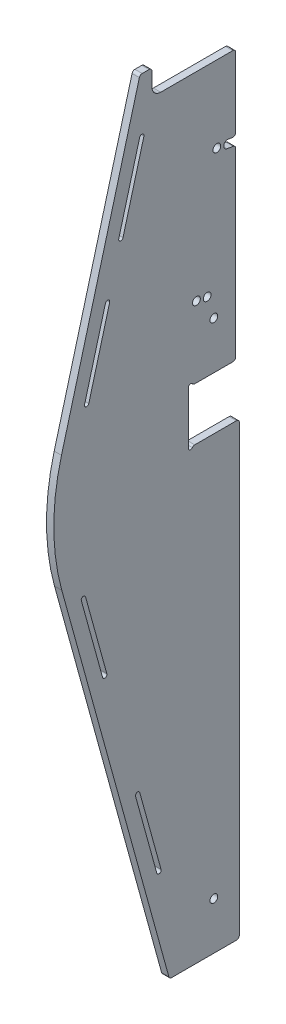
SolidWorks part; units mm, degrees
material "PC High Viscosity"
ref_plane "Front Plane" through (0, 0, 0) normal (0, 0, 1) x (1, 0, 0)
ref_plane "Top Plane" through (0, 0, 0) normal (0, 1, 0) x (1, 0, 0)
ref_plane "Right Plane" through (0, 0, 0) normal (1, 0, 0) x (0, 0, -1)
sketch "ReferenceGeometry" plane through (0, 0, 0) normal (1, 0, 0) x (0, 0, -1)
  line L0 (0, 0) -> (-63.5, -234.95)
  line L1 (-63.5, -234.95) -> (-63.5, -279.4)
  line L2 (31.75, -234.4263) -> (34.8815, -234.95)
  line L3 (76.2, 0) -> (82.55, 0)
  line L4 (31.75, -234.95) -> (76.2, -234.95)
  line L5 (31.75, -234.95) -> (31.75, -279.4)
  line L6 (31.75, -279.4) -> (76.2, -279.4)
  line L7 (76.2, -234.95) -> (76.2, -279.4)
  line L8 (31.75, -673.1) -> (76.2, -673.1)
  line L9 (31.75, -673.1) -> (31.75, -717.55)
  line L10 (31.75, -717.55) -> (76.2, -717.55)
  line L11 (76.2, -673.1) -> (76.2, -717.55)
  line L12 (31.75, -234.4263) -> (69.8935, -6.35)
  line L13 (34.8815, -234.95) -> (73.025, -6.8737)
  line L14 (69.8935, -6.35) -> (73.025, -6.8737)
  line L15 (-63.5, -279.4) -> (31.75, -673.1)
  line L17 (76.2, 0) -> (73.025, 0)
  line L18 (76.2, 0) -> (76.2, -234.95)
  line L19 (76.2, -234.95) -> (73.025, -234.95)
  line L20 (73.025, 0) -> (73.025, -234.95)
  line L21 (0, 0) -> (6.35, 0) construction
  line L22 (0, 0) -> (0, 50.8) construction
  line L23 (0, 50.8) -> (6.35, 50.8) construction
  line L24 (6.35, 0) -> (6.35, 50.8) construction
  dimension "D1" = 44.45
  dimension "D2" = 438.15
  dimension "D3" = 6.35
  dimension "D4" = 6.35
  dimension "D5" = 234.95
  dimension "D6" = 3.175
  dimension "D7" = 3.175
  dimension "D8" = 6.35
  dimension "D9" = 95.25
  dimension "D10" = 231.2439
  dimension "D11" = 50.8
  dimension "D12" = 66.675
sketch "CoreWall" plane through (0, 0, 0) normal (1, 0, 0) x (0, 0, -1)
  line L0 (73.025, -234.95) -> (31.75, -234.95)
  line L1 (0, 0) -> (73.025, 0)
  line L2 (73.025, -234.95) -> (73.025, 0)
  line L3 (31.75, -234.95) -> (31.75, -280.9875)
  line L4 (31.75, -280.9875) -> (76.2, -280.9875)
  line L5 (76.2, -234.95) -> (76.2, -279.4) construction
  line L6 (31.75, -279.4) -> (76.2, -279.4) construction
  line L7 (76.2, -280.9875) -> (76.2, -673.1)
  line L8 (76.2, -673.1) -> (31.75, -673.1)
  line L9 (0, 0) -> (-63.5, -234.95)
  line L10 (-63.2591, -328.6115) -> (31.75, -673.1)
  arc A0 (-63.5, -234.95) -> (-63.2591, -328.6115) centre (108.1416, -281.3396) ccw
  dimension "D2" = 177.8
  dimension "D1" = 1.5875
sketch "WallTabAdder" plane through (0, 0, 0) normal (1, 0, 0) x (0, 0, -1)
  line L0 (0, 0) -> (-63.5, -234.95) construction
  line L1 (-63.2591, -328.6115) -> (31.75, -673.1) construction
  line L2 (0, 0) -> (-63.5, -234.95)
  line L3 (-63.2591, -328.6115) -> (31.75, -673.1)
  line L4 (-16.4446, 0) -> (-78.8251, -230.8081)
  line L5 (-78.5627, -332.8322) -> (15.2823, -673.1)
  line L6 (-78.5627, -332.8322) -> (16.4464, -677.3207) construction
  line L7 (15.2823, -673.1) -> (31.75, -673.1)
  line L8 (-15.3251, 4.1419) -> (-78.8251, -230.8081) construction
  line L9 (-16.4446, 0) -> (0, 0)
  line L10 (-27.0627, -92.8306) -> (-8.8382, -25.4) construction
  line L11 (-28.9017, -92.3336) -> (-10.6772, -24.903)
  line L12 (-25.2237, -93.3277) -> (-6.9992, -25.897)
  line L13 (6.1311, -587.375) -> (-12.44, -520.039) construction
  line L14 (4.2947, -587.8815) -> (-14.2764, -520.5455)
  line L15 (7.9676, -586.8685) -> (-10.6035, -519.5325)
  line L16 (-41.1408, -415.9743) -> (-59.7119, -348.6383) construction
  line L17 (-42.9772, -416.4808) -> (-61.5483, -349.1448)
  line L18 (-39.3044, -415.4678) -> (-57.8755, -348.1318)
  line L19 (-56.8846, -203.1717) -> (-38.6601, -135.741) construction
  line L20 (-58.7236, -202.6746) -> (-40.4991, -135.244)
  line L21 (-55.0456, -203.6687) -> (-36.8211, -136.2381)
  arc A0 (-63.5, -234.95) -> (-63.2591, -328.6115) centre (108.1416, -281.3396) ccw construction
  arc A1 (-63.5, -234.95) -> (-63.2591, -328.6115) centre (108.1416, -281.3396) ccw
  arc A2 (-78.8251, -230.8081) -> (-78.5627, -332.8322) centre (108.1416, -281.3396) ccw
  arc A3 (-28.9017, -92.3336) -> (-25.2237, -93.3277) centre (-27.0627, -92.8306) ccw
  arc A4 (-6.9992, -25.897) -> (-10.6772, -24.903) centre (-8.8382, -25.4) ccw
  arc A5 (4.2947, -587.8815) -> (7.9676, -586.8685) centre (6.1311, -587.375) ccw
  arc A6 (-10.6035, -519.5325) -> (-14.2764, -520.5455) centre (-12.44, -520.039) ccw
  arc A7 (-42.9772, -416.4808) -> (-39.3044, -415.4678) centre (-41.1408, -415.9743) ccw
  arc A8 (-57.8755, -348.1318) -> (-61.5483, -349.1448) centre (-59.7119, -348.6383) ccw
  arc A9 (-58.7236, -202.6746) -> (-55.0456, -203.6687) centre (-56.8846, -203.1717) ccw
  arc A10 (-36.8211, -136.2381) -> (-40.4991, -135.244) centre (-38.6601, -135.741) ccw
  point P14 (-17.9505, -59.1153)
  point P20 (-3.1544, -553.707)
  point P27 (-50.4263, -382.3063)
  point P35 (-47.7724, -169.4564)
  dimension "D2" = 69.85
  dimension "D3" = 3.81
  dimension "D4" = 25.4
  dimension "D5" = 85.725
  dimension "D6" = 107.95
  dimension "D7" = 44.45
  dimension "D1" = 15.875
sketch "Sketch4" plane through (0, 0, 0) normal (1, 0, 0) x (0, 0, -1)
  line L1 (31.75, -280.9875) -> (76.2, -280.9875) construction
  line L2 (76.2, -280.9875) -> (76.2, -673.1) construction
  line L3 (31.75, -673.1) -> (76.2, -673.1) construction
  line L4 (15.2823, -673.1) -> (31.75, -673.1) construction
  line L5 (-78.5627, -332.8322) -> (15.2823, -673.1) construction
  line L6 (-16.4446, 0) -> (-78.8251, -230.8081) construction
  line L7 (-16.4446, 0) -> (0, 0) construction
  line L8 (0, 0) -> (73.025, 0) construction
  line L9 (73.025, 0) -> (73.025, -234.95) construction
  line L10 (31.75, -234.95) -> (31.75, -280.9875) construction
  line L11 (31.75, -280.9875) -> (76.2, -280.9875)
  line L12 (76.2, -280.9875) -> (76.2, -673.1)
  line L13 (31.75, -673.1) -> (76.2, -673.1)
  line L14 (15.2823, -673.1) -> (31.75, -673.1)
  line L15 (-78.5627, -332.8322) -> (15.2823, -673.1)
  line L16 (-16.4446, 0) -> (-78.8251, -230.8081)
  line L17 (-16.4446, 0) -> (0, 0)
  line L18 (0, 0) -> (73.025, 0)
  line L19 (73.025, 0) -> (73.025, -234.95)
  line L20 (73.025, -234.95) -> (31.75, -234.95)
  line L21 (-28.9017, -92.3336) -> (-10.6772, -24.903) construction
  line L22 (-28.9017, -92.3336) -> (-10.6772, -24.903)
  line L23 (-25.2237, -93.3277) -> (-6.9992, -25.897) construction
  line L24 (-25.2237, -93.3277) -> (-6.9992, -25.897)
  line L25 (31.75, -234.95) -> (31.75, -280.9875)
  line L26 (-42.9772, -416.4808) -> (-61.5483, -349.1448) construction
  line L27 (-42.9772, -416.4808) -> (-61.5483, -349.1448)
  line L28 (-39.3044, -415.4678) -> (-57.8755, -348.1318) construction
  line L29 (-39.3044, -415.4678) -> (-57.8755, -348.1318)
  line L30 (7.9676, -586.8685) -> (-10.6035, -519.5325) construction
  line L31 (7.9676, -586.8685) -> (-10.6035, -519.5325)
  line L32 (4.2947, -587.8815) -> (-14.2764, -520.5455) construction
  line L33 (4.2947, -587.8815) -> (-14.2764, -520.5455)
  line L34 (-58.7236, -202.6746) -> (-40.4991, -135.244) construction
  line L35 (-58.7236, -202.6746) -> (-40.4991, -135.244)
  line L36 (-55.0456, -203.6687) -> (-36.8211, -136.2381) construction
  line L37 (-55.0456, -203.6687) -> (-36.8211, -136.2381)
  arc A0 (-78.8251, -230.8081) -> (-78.5627, -332.8322) centre (108.1416, -281.3396) ccw construction
  arc A1 (-6.9992, -25.897) -> (-10.6772, -24.903) centre (-8.8382, -25.4) ccw construction
  arc A2 (-78.8251, -230.8081) -> (-78.5627, -332.8322) centre (108.1416, -281.3396) ccw
  arc A3 (-6.9992, -25.897) -> (-10.6772, -24.903) centre (-8.8382, -25.4) ccw
  arc A4 (-28.9017, -92.3336) -> (-25.2237, -93.3277) centre (-27.0627, -92.8306) ccw construction
  arc A5 (-28.9017, -92.3336) -> (-25.2237, -93.3277) centre (-27.0627, -92.8306) ccw
  arc A6 (-42.9772, -416.4808) -> (-39.3044, -415.4678) centre (-41.1408, -415.9743) ccw construction
  arc A7 (-57.8755, -348.1318) -> (-61.5483, -349.1448) centre (-59.7119, -348.6383) ccw construction
  arc A8 (-42.9772, -416.4808) -> (-39.3044, -415.4678) centre (-41.1408, -415.9743) ccw
  arc A9 (-57.8755, -348.1318) -> (-61.5483, -349.1448) centre (-59.7119, -348.6383) ccw
  arc A10 (-10.6035, -519.5325) -> (-14.2764, -520.5455) centre (-12.44, -520.039) ccw construction
  arc A11 (-10.6035, -519.5325) -> (-14.2764, -520.5455) centre (-12.44, -520.039) ccw
  arc A12 (4.2947, -587.8815) -> (7.9676, -586.8685) centre (6.1311, -587.375) ccw construction
  arc A13 (4.2947, -587.8815) -> (7.9676, -586.8685) centre (6.1311, -587.375) ccw
  arc A14 (-36.8211, -136.2381) -> (-40.4991, -135.244) centre (-38.6601, -135.741) ccw construction
  arc A15 (-36.8211, -136.2381) -> (-40.4991, -135.244) centre (-38.6601, -135.741) ccw
  arc A16 (-58.7236, -202.6746) -> (-55.0456, -203.6687) centre (-56.8846, -203.1717) ccw construction
  arc A17 (-58.7236, -202.6746) -> (-55.0456, -203.6687) centre (-56.8846, -203.1717) ccw
  point P31 (-56.8846, -203.1717)
extrude "Boss-Extrude1" add sketch "Sketch4" along normal blind 6.35
hole_wizard "1/4 Clearance Hole1" positions "Sketch5" profile "Sketch6" hole size "1/4" standard "ANSI Inch" end condition through all
sketch "Sketch5" plane through (6.35, 0, 0) normal (1, 0, 0) x (0, 0, -1)
  line L0 (53.975, -717.55) -> (53.975, -673.1) construction
  line L1 (31.75, -717.55) -> (76.2, -717.55) construction
  line L2 (31.75, -673.1) -> (76.2, -673.1) construction
  line L3 (53.975, -631.825) -> (53.975, -673.1) construction
  line L4 (53.975, -193.675) -> (53.975, -234.95) construction
  line L5 (31.75, -234.95) -> (76.2, -234.95) construction
  line L6 (45.0501, -174.1475) -> (41.9186, -173.6238) construction
  line L7 (34.8815, -234.95) -> (73.025, -6.8737) construction
  line L8 (31.75, -234.4263) -> (69.8935, -6.35) construction
  line L9 (33.3158, -234.6881) -> (71.4592, -6.6119) construction
  line L10 (31.75, -234.4263) -> (34.8815, -234.95) construction
  line L11 (69.8935, -6.35) -> (73.025, -6.8737) construction
  line L12 (38.7871, -173.1001) -> (56.5934, -66.6288) construction
  line L13 (53.9533, -120.9119) -> (50.8217, -120.3881) construction
  point P0 (53.975, -631.825)
  point P2 (53.975, -193.675)
  point P4 (48.1816, -174.6712)
  point P6 (38.7871, -173.1001)
  point P8 (56.5934, -66.6288)
  dimension "D1" = 41.275
  dimension "D2" = 61.6469
  dimension "D3" = 3.175
  dimension "D4" = 107.95
  dimension "D5" = 231.2439
sketch "Sketch6" plane through (6.35, -631.825, -53.975) normal (0, 1, 0) x (0, 0, -1)
  line L0 (0, 0) -> (0, 6.35)
  line L1 (0, 6.35) -> (3.3782, 6.35)
  line L2 (3.3782, 6.35) -> (3.3782, 0)
  line L5 (3.3782, 0) -> (0, 0)
  line L11 (0, -6.35) -> (0, 107.95) construction
  dimension "Thru Hole Dia." = 6.7564
  dimension "Thru Hole Depth" = 6.35
sketch "Sketch7" plane through (6.35, 0, 0) normal (1, 0, 0) x (0, 0, -1)
  line L0 (48.1816, -174.6712) -> (65.9879, -68.1999) construction
  line L1 (38.7871, -173.1001) -> (56.5934, -66.6288) construction
  line L2 (73.025, -234.95) -> (73.025, 0) construction
  line L3 (73.025, -72.8019) -> (65.4307, -71.5318)
  line L4 (73.025, -72.8019) -> (73.025, -65.9517)
  line L5 (73.025, 0) -> (73.025, -234.95) construction
  line L6 (73.025, -65.9517) -> (66.5451, -64.868)
  circle A0 centre (65.9879, -68.1999) radius 3.3782 construction
  circle A1 centre (56.5934, -66.6288) radius 3.3782 construction
  arc A2 (66.5451, -64.868) -> (65.4307, -71.5318) centre (65.9879, -68.1999) ccw
extrude "Cut-Extrude1" cut sketch "Sketch7" against normal through all
sketch "Sketch9" plane through (6.35, 0, 0) normal (1, 0, 0) x (0, 0, -1)
  line L0 (31.75, -280.9875) -> (31.75, -234.95) construction
  line L1 (31.75, -234.95) -> (73.025, -234.95) construction
  line L2 (76.2, -280.9875) -> (31.75, -280.9875) construction
  circle A0 centre (33.655, -234.95) radius 1.905
  circle A1 centre (33.655, -280.9875) radius 1.905
  dimension "D1" = 3.81
extrude "Cut-Extrude2" cut sketch "Sketch9" against normal through all
sketch "Sketch10" plane through (6.35, 0, 0) normal (1, 0, 0) x (0, 0, -1)
  line L0 (0, 0) -> (0, 22.225)
  line L1 (0, 0) -> (0, 50.8) construction
  line L2 (0, 22.225) -> (-10.4378, 22.225)
  line L3 (-10.4378, 22.225) -> (-16.4446, 0)
  line L4 (-16.4446, 0) -> (-78.8251, -230.8081) construction
  line L5 (-16.4446, 0) -> (0, 0)
  dimension "D1" = 22.225
extrude "Boss-Extrude2" add sketch "Sketch10" against normal up to surface (6.35 mm away) up to face at (0, -631.825, -57.3532)
fillet "Fillet1" radius 2.54 11 edges at (3.175, -280.9875, -35.56) (3.175, -673.1, -76.2) (3.175, -673.1, -15.2823) (3.175, 0, -73.025) (3.175, -65.9517, -73.025) (3.175, -72.8019, -73.025) (3.175, -234.95, -73.025) (3.175, -234.95, -35.56) (3.175, -280.9875, -76.2) (3.175, 22.225, 0) (3.175, 22.225, 10.4378)
fillet "Fillet2" radius 7.62 1 edges at (3.175, 0, 0)
